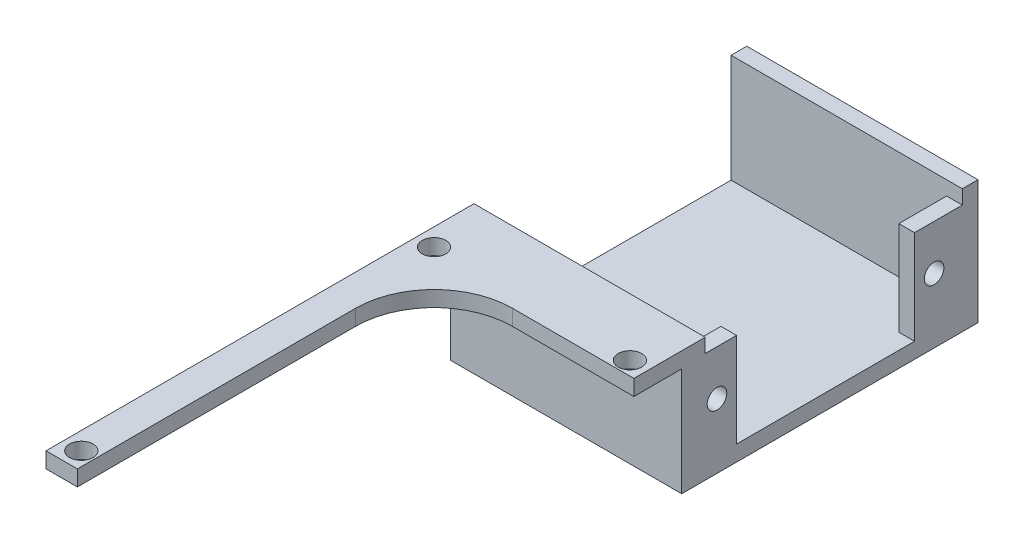
SolidWorks part; units mm, degrees
note: The reader was unsure of these and kept them because the rebuilt part matched: shared geometry of "Sketch9<2>".
ref_plane "Front Plane" through (0, 0, 0) normal (0, 0, 1) x (1, 0, 0)
ref_plane "Top Plane" through (0, 0, 0) normal (0, 1, 0) x (1, 0, 0)
ref_plane "Right Plane" through (0, 0, 0) normal (1, 0, 0) x (0, 0, -1)
sketch "Sketch1" plane through (0, 0, 0) normal (0, 1, 0) x (1, 0, 0)
  line L1 (-41.2344, 16.8984) -> (-37.2344, 16.8984)
  line L2 (-41.2344, 16.8984) -> (-41.2344, -32.6016)
  line L3 (-41.2344, -32.6016) -> (-37.2344, -32.6016)
  line L4 (-37.2344, 16.8984) -> (-37.2344, -32.6016)
  line L5 (-37.2344, 16.8984) -> (-11.7344, 16.8984)
  line L6 (-37.2344, 16.8984) -> (-37.2344, 12.8984)
  line L7 (-37.2344, 12.8984) -> (-11.7344, 12.8984)
  line L8 (-11.7344, 16.8984) -> (-11.7344, 12.8984)
  dimension "D1" = 49.5
  dimension "D2" = 4
  dimension "D3" = 25.5
  dimension "D4" = 4
extrude "Boss-Extrude1" add sketch "Sketch1" along normal blind 2 contours L8 L5 L4 L7
sketch "Sketch2" plane through (0, 2, 0) normal (0, 1, 0) x (1, 0, 0)
  line L0 (-41.2344, 16.8984) -> (-41.2344, -32.6016) construction
  line L1 (-41.2344, -32.6016) -> (-37.2344, -32.6016) construction
  line L2 (-41.2344, 16.8984) -> (-11.7344, 16.8984) construction
  circle A0 centre (-38.9844, -30.3516) radius 1.5
  circle A1 centre (-38.9844, 14.6484) radius 1.5
  circle A2 centre (-13.9844, 14.6484) radius 1.5
  point P12 (0, 0)
  point P13 (0, 0)
  point P14 (0, 0)
  dimension "D1" = 3
  dimension "D2" = 2.25
  dimension "D3" = 3
  dimension "D4" = 45
  dimension "D5" = 2.25
  dimension "D6" = 2.25
  dimension "D7" = 3
  dimension "D8" = 25
fillet "Fillet1" radius 10 1 edges at (-37.2344, 1, -12.8984)
extrude "Cut-Extrude1" cut sketch "Sketch2" against normal through all
sketch "Sketch3" plane through (0, 0, -16.8984) normal (0, 0, -1) x (-1, 0, 0)
  line L4 (11.7344, 0) -> (41.2344, 0)
  line L5 (41.2344, 0) -> (41.2344, 2)
  line L6 (41.2344, 2) -> (11.7344, 2)
  line L7 (11.7344, 2) -> (11.7344, 0)
  line L8 (11.7344, 0) -> (41.2344, 0)
  line L9 (41.2344, 0) -> (41.2344, 2)
  line L10 (41.2344, 2) -> (11.7344, 2)
  line L11 (11.7344, 2) -> (11.7344, 0)
  dimension "D1" = 0
extrude "Boss-Extrude2" add sketch "Sketch3" along normal blind 5.1
sketch "Sketch4" plane through (0, 0, 0) normal (0, -1, 0) x (1, 0, 0)
  line L0 (-41.2344, -21.9984) -> (-41.2344, 32.6016) construction
  line L1 (-11.7344, -21.9984) -> (-41.2344, -21.9984)
  line L2 (-11.7344, -21.9984) -> (-11.7344, -18.9984)
  line L3 (-11.7344, -18.9984) -> (-41.2344, -18.9984)
  line L4 (-41.2344, -21.9984) -> (-41.2344, -18.9984)
  dimension "D1" = 3
extrude "Boss-Extrude3" add sketch "Sketch4" along normal blind 13.8
sketch "Sketch5" plane through (0, 0, -21.9984) normal (0, 0, -1) x (-1, 0, 0)
  line L0 (11.7344, 2) -> (11.7344, -13.8) construction
  line L1 (11.7344, -11.8) -> (41.2344, -11.8)
  line L2 (11.7344, -11.8) -> (11.7344, -13.8)
  line L3 (11.7344, -13.8) -> (41.2344, -13.8)
  line L4 (41.2344, -11.8) -> (41.2344, -13.8)
  dimension "D1" = 2
extrude "Boss-Extrude5" add sketch "Sketch5" along normal blind 34.8
sketch "Sketch7" plane through (0, -11.8, 0) normal (0, 1, 0) x (1, 0, 0)
  line L0 (-11.7344, 56.7984) -> (-11.7344, 21.9984) construction
  line L1 (-41.2344, 56.7984) -> (-11.7344, 56.7984)
  line L2 (-41.2344, 56.7984) -> (-41.2344, 54.7984)
  line L3 (-41.2344, 54.7984) -> (-11.7344, 54.7984)
  line L4 (-11.7344, 56.7984) -> (-11.7344, 54.7984)
  dimension "D1" = 2
extrude "Boss-Extrude6" add sketch "Sketch7" along normal blind 13.8
sketch "Sketch8" plane through (0, -11.8, 0) normal (0, 1, 0) x (1, 0, 0)
  line L1 (-11.7344, 21.9984) -> (-13.7344, 21.9984)
  line L2 (-11.7344, 21.9984) -> (-11.7344, 25.9984)
  line L3 (-11.7344, 25.9984) -> (-13.7344, 25.9984)
  line L4 (-13.7344, 21.9984) -> (-13.7344, 25.9984)
  line L5 (-11.7344, 54.7984) -> (-13.7344, 54.7984)
  line L6 (-11.7344, 54.7984) -> (-11.7344, 48.6984)
  line L7 (-11.7344, 48.6984) -> (-13.7344, 48.6984)
  line L8 (-13.7344, 54.7984) -> (-13.7344, 48.6984)
  dimension "D1" = 4
  dimension "D2" = 6.1
  dimension "D3" = 2
  dimension "D4" = 2
extrude "Boss-Extrude7" add sketch "Sketch8" along normal blind 12
sketch "Sketch9" plane through (-11.7344, 0, 0) normal (1, 0, 0) x (0, 0, -1)
  line L0 (25.9984, 0.2) -> (25.9984, -11.8) construction
  line L1 (48.6984, 0.2) -> (48.6984, -11.8) construction
  line L2 (48.6984, -11.8) -> (25.9984, -11.8) construction
  circle A0 centre (23.4984, -5.55) radius 1.25
  circle A1 centre (51.1984, -5.55) radius 1.25
  point P4 (0, 0)
  dimension "D1" = 2.5
  dimension "D2" = 2.5
  dimension "D4" = 6.25
  dimension "D5" = 2.5
  dimension "D3" = 6.25
  dimension "D6" = 2.5
extrude "Cut-Extrude3" cut sketch "Sketch9<2>" against normal blind 12
sketch "Sketch9<2>" plane through (-11.7344, 0, 0) normal (1, 0, 0) x (0, 0, -1) same geometry as "Sketch9"
extrude "Cut-Extrude2" cut sketch "Sketch9" against normal blind 12
